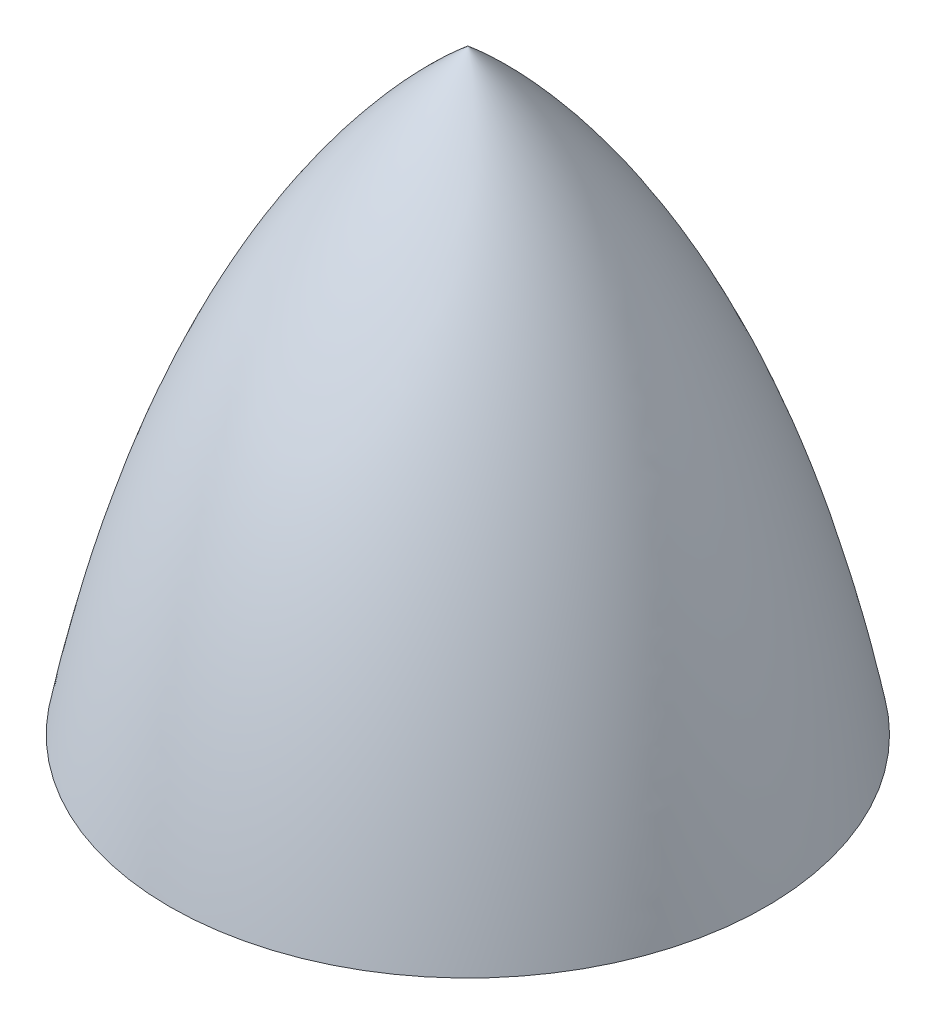
SolidWorks part; units mm, degrees
material "1060 Alloy"
ref_plane "Front Plane" through (0, 0, 0) normal (0, 0, 1) x (1, 0, 0)
ref_plane "Top Plane" through (0, 0, 0) normal (0, 1, 0) x (1, 0, 0)
ref_plane "Right Plane" through (0, 0, 0) normal (1, 0, 0) x (0, 0, -1)
sketch "Sketch1" plane through (0, 0, 0) normal (0, 0, 1) x (1, 0, 0)
  line L0 (0, 0) -> (0, 101.6)
  line L1 (0, 0) -> (-50.8, 0)
  line L2 (0, 0) -> (-130.3555, 0) construction
  line L3 (0, 0) -> (0, -49.0041) construction
  spline S0 degree 3 poles (-50.8, 0) (-43.684, 37.1735) (-29.6989, 76.3338) (0, 101.6) knots 0 0 0 0 1 1 1 1
  dimension "D1" = 101.6
  dimension "D2" = 50.8
  dimension "D6" = 18.2437
  dimension "D8" = 40.7518
  dimension "D10" = 38.1535
  dimension "D12" = 81.9693
revolve "Revolve1" add sketch "Sketch1" angle 360 about L3
shell "Shell2" thickness 2.54 removed face at (0, 0, 50.8)
